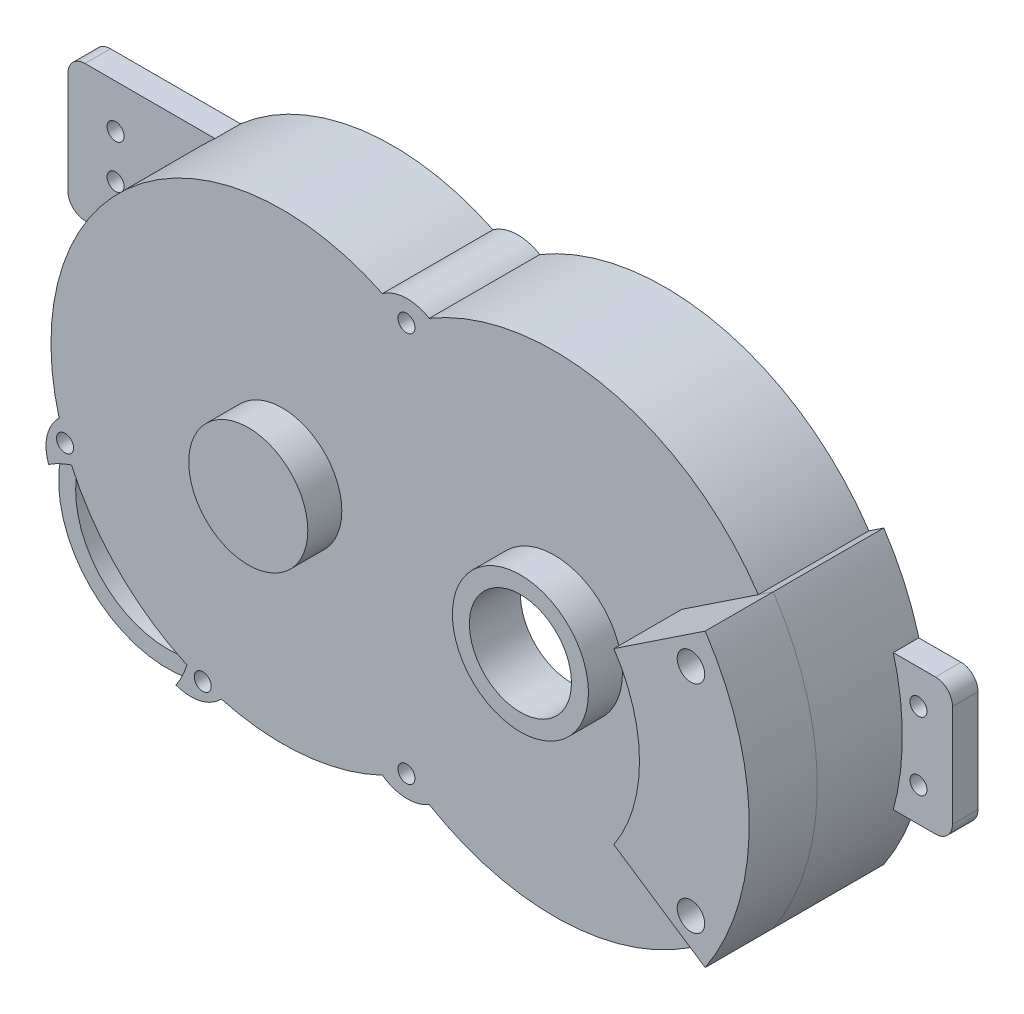
SolidWorks part; units mm, degrees
material "7075-T6 (SN)"
ref_plane "Front Plane" through (0, 0, 0) normal (0, 0, 1) x (1, 0, 0)
ref_plane "Top Plane" through (0, 0, 0) normal (0, 1, 0) x (1, 0, 0)
ref_plane "Right Plane" through (0, 0, 0) normal (1, 0, 0) x (0, 0, -1)
sketch "Sketch1" plane through (0, 0, 0) normal (0, 0, 1) x (1, 0, 0)
  line L0 (-80, 0) -> (-127.9844, 48.1819)
  line L1 (92, 0) -> (92, 15)
  line L2 (92, 0) -> (92, -15)
  line L3 (87, 20) -> (69.1665, 20)
  line L4 (87, -20) -> (69.1665, -20)
  line L7 (-168, 16.1707) -> (-168, 46.1707)
  line L8 (-163, 51.1707) -> (-124.7835, 51.1707)
  line L12 (-123.7096, 66.5348) -> (-123.6577, 66.5865)
  line L14 (-168, 51.1707) -> (-168, 11.1707)
  line L16 (-163, 11.1707) -> (-147.0762, 11.1707)
  arc A0 (-43.25, -51.1707) -> (-43.25, 51.1707) centre (0, 0) ccw
  arc A1 (-43.25, 51.1707) -> (-136.9532, -26.932) centre (-80, 0) ccw
  arc A2 (-136.9532, -26.932) -> (-106.932, -56.9532) centre (-133.7401, -53.7401) ccw
  arc A6 (-106.932, -56.9532) -> (-43.25, -51.1707) centre (-80, 0) ccw
  arc A7 (-36.8059, -61.8816) -> (-36.8059, 61.8816) centre (0, 0) ccw
  arc A8 (-145.6003, -17.9054) -> (-149.4051, -25.8366) centre (-136.9532, -26.932) ccw
  circle A9 centre (-143.8541, -23.3805) radius 2.5
  arc A10 (-36.8059, 61.8816) -> (-50.5714, 61.3022) centre (-43.25, 51.1707) ccw
  circle A11 centre (-43.5, 57.3738) radius 2.5
  arc A12 (-105.8366, -69.4051) -> (-97.9054, -65.6003) centre (-106.932, -56.9532) ccw
  arc A13 (-50.5714, -61.3022) -> (-36.8059, -61.8816) centre (-43.25, -51.1707) ccw
  circle A14 centre (-103.3805, -63.8541) radius 2.5
  circle A15 centre (-43.5, -57.3738) radius 2.5
  arc A16 (-149.4051, -25.8366) -> (-105.8366, -69.4051) centre (-133.7401, -53.7401) ccw
  arc A17 (-50.5714, 61.3022) -> (-145.6003, -17.9054) centre (-80, 0) ccw
  arc A18 (-97.9054, -65.6003) -> (-50.5714, -61.3022) centre (-80, 0) ccw
  circle A19 centre (82, 10) radius 2.5
  circle A20 centre (82, -10) radius 2.5
  arc A21 (92, -15) -> (87, -20) centre (87, -15) cw
  arc A22 (92, 15) -> (87, 20) centre (87, 15) ccw
  circle A23 centre (0, 0) radius 15
  circle A24 centre (-80, 0) radius 12.5
  circle A25 centre (-133.7401, -53.7401) radius 10
  circle A26 centre (0, 0) radius 20
  circle A27 centre (-80, 0) radius 17.5
  circle A28 centre (-133.7401, -53.7401) radius 15
  circle A29 centre (-154, 38.378) radius 2.5
  circle A30 centre (-154, 25.5853) radius 2.5
  arc A31 (-168, 46.1707) -> (-163, 51.1707) centre (-163, 46.1707) cw
  arc A32 (-168, 16.1707) -> (-163, 11.1707) centre (-163, 16.1707) ccw
  point P39 (92, -20)
  point P42 (92, 20)
  point P53 (-138.6899, 72.832)
  dimension "D1" = 134
  dimension "D3" = 126
  dimension "D5" = 54
  dimension "D6" = 20
  dimension "D7" = 20
  dimension "D8" = 5
  dimension "D9" = 5
  dimension "D10" = 25
  dimension "D11" = 25
  dimension "D12" = 5
  dimension "D13" = 25
  dimension "D14" = 5
  dimension "D15" = 25
  dimension "D16" = 5
  dimension "D17" = 5
  dimension "D18" = 5
  dimension "D19" = 30
  dimension "D20" = 25
  dimension "D21" = 20
  dimension "D22" = 40
  dimension "D23" = 35
  dimension "D24" = 30
  dimension "D28" = 5
  dimension "D25" = 5
  dimension "D27" = 40
  dimension "D29" = 5
  dimension "D2" = 80
  dimension "D4" = 76
extrude "Boss-Extrude5" add sketch "Sketch1" against normal blind 5 contours A2 A6 A0 A1 A28 A27 A26 | A27 A24 | A26 A23 region at (-73.4763, 15.7039, 0) region at (-42.4728, -3.1282, 0) region at (-19.4343, 0, 0)
extrude "Boss-Extrude6" add sketch "Sketch1<10>" against normal blind 32.5 contours A12 A18 A13 A7 A10 A17 A8 A16 A6 A2 A1 A0 A9 A11 A14 A15 | L1 A22 L3 A7 L4 A21 L2 A19 A20 region at (-124.4609, 47.6167, 0) region at (81.3627, 0, 0)
sketch "Sketch1<10>" plane through (0, 0, 0) normal (0, 0, 1) x (1, 0, 0) same geometry as "Sketch1"
extrude "Cut-Extrude3" cut sketch "Sketch1<11>" against normal blind 25 contours L1 A22 L3 A7 L4 A21 L2 A19 A20 region at (81.3627, 0, 0)
sketch "Sketch1<11>" plane through (0, 0, 0) normal (0, 0, 1) x (1, 0, 0) same geometry as "Sketch1"
extrude "Boss-Extrude7" add sketch "Sketch1<12>" along normal blind 10 contours A27 A24 | A26 A23 | A24 region at (-73.4763, 15.7039, 0) region at (-75.3402, 11.2171, 0) region at (-19.4343, 0, 0)
sketch "Sketch1<12>" plane through (0, 0, 0) normal (0, 0, 1) x (1, 0, 0) same geometry as "Sketch1"
extrude "Cut-Extrude4" cut sketch "Sketch1<13>" along normal blind 5 contours A24 region at (-75.3402, 11.2171, 0)
sketch "Sketch1<13>" plane through (0, 0, 0) normal (0, 0, 1) x (1, 0, 0) same geometry as "Sketch1"
extrude "Boss-Extrude8" add sketch "Sketch1<14>" against normal blind 5 contours A28 A25 | A25 region at (-133.7401, -53.7401, 0) region at (-148.3159, -53.7401, 0)
sketch "Sketch1<14>" plane through (0, 0, 0) normal (0, 0, 1) x (1, 0, 0) same geometry as "Sketch1"
sketch "Sketch3" plane through (0, 0, 0) normal (0, 0, 1) x (1, 0, 0)
  arc A0 (-143.8541, -23.3805) -> (-103.3805, -63.8541) centre (-80, 0) ccw
  arc A1 (-138.9701, -22.1704) -> (-102.1704, -58.9701) centre (-80, 0) ccw
  arc A2 (-138.9701, -22.1704) -> (-102.1704, -58.9701) centre (-133.7401, -53.7401) ccw
  arc A3 (-136.9532, -26.932) -> (-106.932, -56.9532) centre (-133.7401, -53.7401) ccw
  dimension "D1" = 126
  dimension "D2" = 54
extrude "Boss-Extrude18" add sketch "Sketch3" against normal blind 30 contours A0 A3 | A1 A3 A0 region at (-125.39, -45.39, 0) region at (-138.3343, -58.3343, 0)
extrude "Cut-Extrude6" cut sketch "Sketch3<3>" against normal blind 25 contours A0 A3 region at (-138.3343, -58.3343, 0)
sketch "Sketch3<3>" plane through (0, 0, 0) normal (0, 0, 1) x (1, 0, 0) same geometry as "Sketch3"
sketch "Sketch4" plane through (0, 0, 0) normal (0, 0, 1) x (1, 0, 0)
  arc A0 (-149.4051, -25.8366) -> (-148.6829, -31.2521) centre (-136.9532, -26.932) ccw
  arc A1 (-111.2521, -68.6829) -> (-105.8366, -69.4051) centre (-106.932, -56.9532) ccw
  arc A2 (-148.6829, -31.2521) -> (-111.2521, -68.6829) centre (-133.7401, -53.7401) ccw
  arc A3 (-149.4051, -25.8366) -> (-105.8366, -69.4051) centre (-133.7401, -53.7401) ccw
extrude "Cut-Extrude7" cut sketch "Sketch4" against normal blind 20
extrude "Boss-Extrude19" add sketch "Sketch1<17>" against normal blind 32.5 contours L7 A32 L16 A17 L8 A31 A29 A30 region at (-152.6108, 33.7326, 0)
sketch "Sketch1<17>" plane through (0, 0, 0) normal (0, 0, 1) x (1, 0, 0) same geometry as "Sketch1"
extrude "Cut-Extrude8" cut sketch "Sketch1<18>" against normal blind 25 contours L7 A32 L16 A17 L8 A31 A29 A30 region at (-152.6108, 33.7326, 0)
sketch "Sketch1<18>" plane through (0, 0, 0) normal (0, 0, 1) x (1, 0, 0) same geometry as "Sketch1"
sketch "Sketch5" plane through (0, 0, 0) normal (0, 0, 1) x (1, 0, 0)
  line L1 (37.4538, -24.9442) -> (64.304, -42.8265)
  line L2 (37.4538, 24.9442) -> (64.304, 42.8265)
  circle A0 centre (60.1326, 31.75) radius 4.05
  arc A1 (64.304, -42.8265) -> (64.304, 42.8265) centre (0, 0) ccw
  circle A2 centre (60.1326, -31.75) radius 4.05
  arc A4 (37.4538, -24.9442) -> (37.4538, 24.9442) centre (0, 0) ccw
  arc A5 (59.926, -39.9108) -> (59.926, 39.9108) centre (0, 0) ccw
  arc M18 (-36.8059, -61.8816) -> (-36.8059, 61.8816) centre (0, 0) ccw
  dimension "D3" = 154.52
  dimension "D7" = 8.1
  dimension "D1" = 90
  dimension "D4" = 8.1
extrude "Boss-Extrude23" add sketch "Sketch5" along normal blind 20 contours A4 L1 A2 A0 L2 M18 | A2 L1 A1 L2 A0 M18 region at (55.9391, 0, 0) region at (62.4596, -37.542, 0)
extrude "Boss-Extrude24" add sketch "Sketch5<7>" along normal blind 10 contours A2 M18 | A0 M18 | A0 | A2 region at (60.1296, -31.7484, 0) region at (60.1296, 31.7484, 0)
sketch "Sketch5<7>" plane through (0, 0, 0) normal (0, 0, 1) x (1, 0, 0) same geometry as "Sketch5"
extrude "Boss-Extrude25" add sketch "Sketch5<8>" against normal blind 32.5 separate body contours A2 L1 A1 L2 A0 M18 region at (62.4596, -37.542, 0)
sketch "Sketch5<8>" plane through (0, 0, 0) normal (0, 0, 1) x (1, 0, 0) same geometry as "Sketch5"
